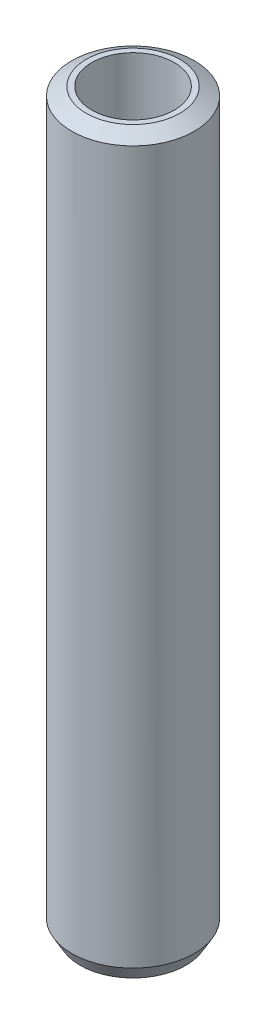
SolidWorks part; units mm, degrees
ref_plane "Front Plane" through (0, 0, 0) normal (0, 0, 1) x (1, 0, 0)
ref_plane "Top Plane" through (0, 0, 0) normal (0, 1, 0) x (1, 0, 0)
ref_plane "Right Plane" through (0, 0, 0) normal (1, 0, 0) x (0, 0, -1)
sketch "Sketch1" plane through (0, 0, 0) normal (0, 1, 0) x (1, 0, 0)
  circle A0 centre (0, 0) radius 12.5
  dimension "SHAFT_OD" = 25
extrude "Boss-Extrude1" add sketch "Sketch1" along normal blind 149.9658
sketch "Sketch2" plane through (0, 0, 0) normal (0, 1, 0) x (1, 0, 0)
  circle A0 centre (0, 0) radius 8.4211
  dimension "BORE_D" = 16.8423
extrude "Cut-Extrude1" cut sketch "Sketch2" along normal through all
chamfer "Chamfer1" distance 1.701 angle 60 2 edges at (0, 149.9658, 12.5) (0, 0, 12.5) first distance on face at (0, 149.9658, 12.5) first distance on face at (0, 0, 8.4211)
